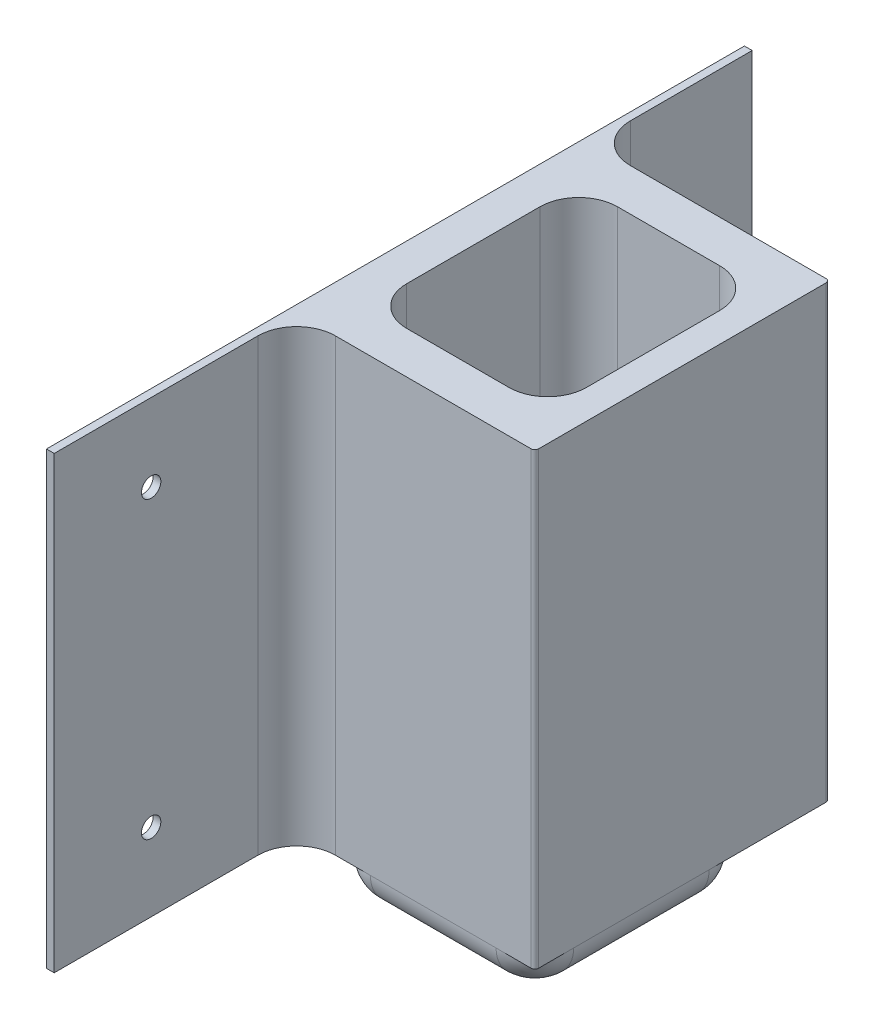
SolidWorks part; units mm, degrees
material "6061 Alloy"
ref_plane "Front Plane" through (0, 0, 0) normal (0, 0, 1) x (1, 0, 0)
ref_plane "Top Plane" through (0, 0, 0) normal (0, 1, 0) x (1, 0, 0)
ref_plane "Right Plane" through (0, 0, 0) normal (1, 0, 0) x (0, 0, -1)
sketch "Sketch1" plane through (0, 0, 0) normal (1, 0, 0) x (0, 0, -1)
  line L1 (-90, -58) -> (90, -58)
  line L2 (-90, -58) -> (-90, 58)
  line L3 (-90, 58) -> (90, 58)
  line L4 (90, -58) -> (90, 58)
  line L5 (-90, -58) -> (90, 58) construction
  line L6 (-90, 58) -> (90, -58) construction
  point P0 (0, 0)
  dimension "D1" = 116
  dimension "D2" = 180
extrude "Boss-Extrude1" add sketch "Sketch1" along normal blind 2
sketch "Sketch9" plane through (0, 0, 0) normal (0, 1, 0) x (1, 0, 0)
  line L4 (19.5345, -16.6223) -> (45.8945, -16.6223)
  line L5 (9.5345, -6.6223) -> (9.5345, 27.7377)
  line L10 (19.5345, 37.7377) -> (45.8945, 37.7377)
  line L11 (55.8945, -6.6223) -> (55.8945, 27.7377)
  line L13 (9.5345, -16.6223) -> (55.8945, 37.7377) construction
  line L14 (9.5345, 37.7377) -> (55.8945, -16.6223) construction
  line L15 (20, -27.4709) -> (62.452, -27.4709)
  line L16 (2, -27.673) -> (2, 27.673)
  line L17 (20, 48.5863) -> (62.452, 48.5863)
  line L18 (63.4291, -26.4938) -> (63.4291, 47.6092)
  line L19 (2, -27.4709) -> (63.4291, 48.5863) construction
  line L20 (2, 48.5863) -> (63.4291, -27.4709) construction
  line L21 (-1.1, 0) -> (1.1, 0) construction
  line L22 (2, 90) -> (2, -90) construction
  line L23 (20, 48.5863) -> (2, 48.5863)
  line L24 (2, 48.5863) -> (2, -27.4709)
  line L25 (2, -27.4709) -> (20, -27.4709)
  arc A8 (62.452, -27.4709) -> (63.4291, -26.4938) centre (62.452, -26.4938) ccw
  arc A9 (62.452, 48.5863) -> (63.4291, 47.6092) centre (62.452, 47.6092) cw
  arc A12 (19.5345, -16.6223) -> (9.5345, -6.6223) centre (19.5345, -6.6223) cw
  arc A13 (45.8945, -16.6223) -> (55.8945, -6.6223) centre (45.8945, -6.6223) ccw
  arc A14 (45.8945, 37.7377) -> (55.8945, 27.7377) centre (45.8945, 27.7377) cw
  arc A15 (9.5345, 27.7377) -> (19.5345, 37.7377) centre (19.5345, 27.7377) cw
  point P0 (32.7145, 10.5577)
  point P5 (32.7145, 10.5577)
  point P34 (2, 0)
  dimension "D1" = 0
extrude "Boss-Extrude6" add sketch "Sketch9" against normal up to surface and the other way up to surface contours A9 L17 L23 L24 L16 L25 L15 A8 L18 L5 A15 L10 A14 L11 A13 L4 A12 region at (11, 0, 26.4932) up to face at (1, -58, 0) other way up to face at (1, 58, 0)
fillet "Fillet5" radius 10 2 edges at (2, 0, 27.4709) (2, 0, -48.5863)
sketch "Sketch11" plane through (0, -58, 0) normal (0, -1, 0) x (1, 0, 0)
  line L0 (1.1, 0) -> (-1.1, 0) construction
  line L1 (21.0229, -27.4709) -> (53.4291, -27.4709)
  line L2 (11.0229, -17.4709) -> (11.0229, 17.4709)
  line L3 (21.0229, 27.4709) -> (53.4291, 27.4709)
  line L4 (63.4291, -17.4709) -> (63.4291, 17.4709)
  line L5 (11.0229, -27.4709) -> (63.4291, 27.4709) construction
  line L6 (11.0229, 27.4709) -> (63.4291, -27.4709) construction
  line L7 (62.452, 27.4709) -> (12, 27.4709) construction
  line L8 (63.4291, -47.6092) -> (63.4291, 26.4938) construction
  arc A0 (53.4291, -27.4709) -> (63.4291, -17.4709) centre (53.4291, -17.4709) ccw
  arc A1 (21.0229, -27.4709) -> (11.0229, -17.4709) centre (21.0229, -17.4709) cw
  arc A2 (11.0229, 17.4709) -> (21.0229, 27.4709) centre (21.0229, 17.4709) cw
  arc A3 (53.4291, 27.4709) -> (63.4291, 17.4709) centre (53.4291, 17.4709) cw
  point P0 (37.226, 0)
  point P9 (37.226, 27.4709)
  dimension "D1" = 10
extrude "Boss-Extrude8" add sketch "Sketch11" along normal blind 8.98
fillet "Fillet7" radius 8.98 8 edges at (60.5002, -66.98, -24.542) (37.226, -66.98, -27.4709) (13.9518, -66.98, -24.542) (11.0229, -66.98, 0) (13.9518, -66.98, 24.542) (63.4291, -66.98, 0) (60.5002, -66.98, 24.542) (37.226, -66.98, 27.4709)
hole_wizard "M6x1.0 Tapped Hole1" positions "Sketch12" profile "Sketch13" tap size "M6x1.0" standard "ANSI Metric" end condition up to next
sketch "Sketch12" plane through (2, 0, 0) normal (1, 0, 0) x (0, 0, -1)
  line L0 (58.5863, -58) -> (90, -58) construction
  line L1 (90, 58) -> (58.5863, 58) construction
  point P0 (-65, 38)
  point P2 (-65, -38)
  point P4 (65, -38)
  point P6 (65, 38)
  dimension "D1" = 65
  dimension "D2" = 65
  dimension "D3" = 20
  dimension "D4" = 20
sketch "Sketch13" plane through (2, 38, 65) normal (0, 1, 0) x (0, 0, -1)
  line L0 (0, 0) -> (0, 2)
  line L1 (0, 2) -> (2.5, 2)
  line L2 (2.5, 2) -> (2.5, 0)
  line L5 (2.5, 0) -> (0, 0)
  line L11 (0, -6.35) -> (0, 107.95) construction
  dimension "Thru Tap Drill Dia." = 5
  dimension "Thru Tap Drill Depth" = 2
cosmetic thread "Hole Thread1" parameters "D2"=6
cosmetic thread "Hole Thread2" parameters "D2"=6
cosmetic thread "Hole Thread3" parameters "D2"=6
cosmetic thread "Hole Thread4" parameters "D2"=6
